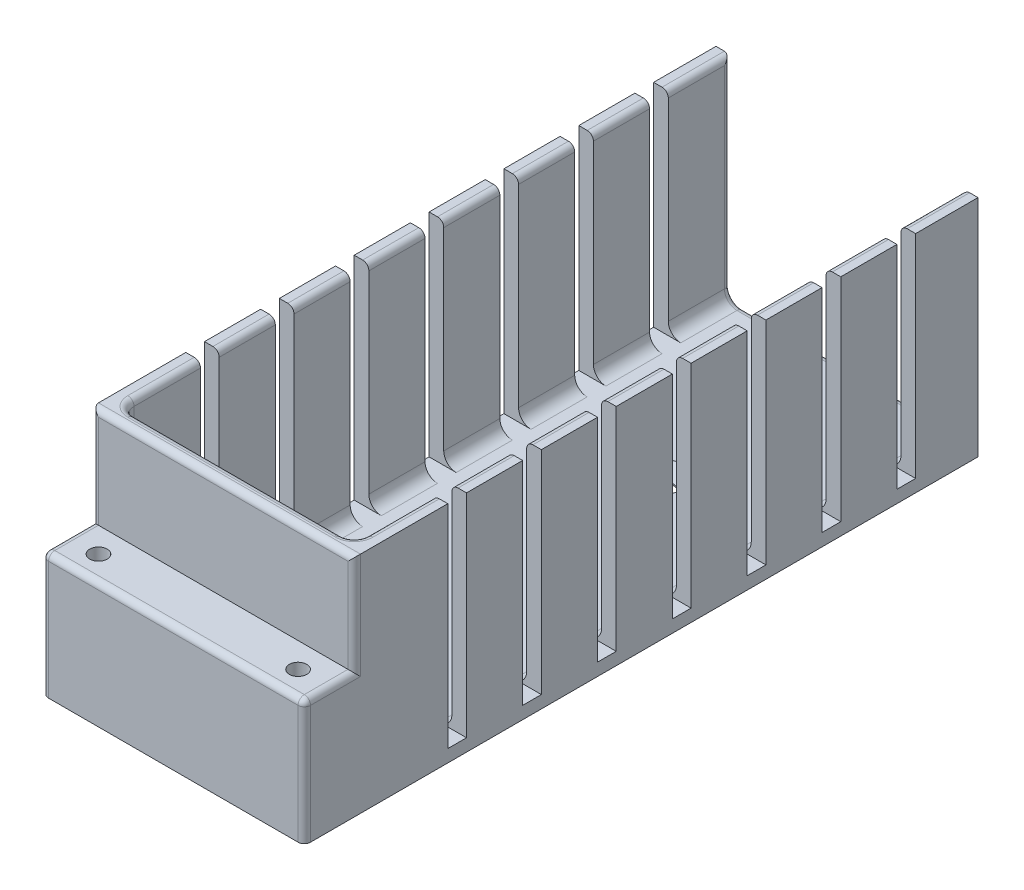
SolidWorks part; units mm, degrees
ref_plane "Front Plane" through (0, 0, 0) normal (0, 0, 1) x (1, 0, 0)
ref_plane "Top Plane" through (0, 0, 0) normal (0, 1, 0) x (1, 0, 0)
ref_plane "Right Plane" through (0, 0, 0) normal (1, 0, 0) x (0, 0, -1)
sketch "Sketch1" plane through (0, 0, 0) normal (0, 1, 0) x (1, 0, 0)
  line L1 (-21, -50) -> (21, -50)
  line L2 (-21, -50) -> (-21, 50)
  line L3 (-21, 50) -> (21, 50)
  line L4 (21, -50) -> (21, 50)
  line L5 (-21, -50) -> (21, 50) construction
  line L6 (-21, 50) -> (21, -50) construction
  point P0 (0, 0)
  dimension "D1" = 42
  dimension "D2" = 100
extrude "Boss-Extrude1" add sketch "Sketch1" along normal blind 2
sketch "Sketch2" plane through (0, 2, 0) normal (0, 1, 0) x (1, 0, 0)
  line L0 (-21, 50) -> (-18.65, 50)
  line L1 (21, 50) -> (-21, 50) construction
  line L2 (-18.65, 50) -> (-18.65, -47.65)
  line L3 (-18.65, -47.65) -> (18.65, -47.65)
  line L4 (21, -50) -> (21, 50)
  line L5 (21, 50) -> (-21, 50)
  line L6 (-21, 50) -> (-21, -50)
  line L7 (-21, -50) -> (21, -50)
  line L8 (21, -50) -> (21, 50)
  line L10 (-21, 50) -> (-21, -50)
  line L11 (-21, -50) -> (21, -50)
  line L12 (18.65, -47.65) -> (18.65, 50)
  line L13 (18.65, 50) -> (21, 50)
  line L14 (0, -47.65) -> (0, 0) construction
  line L15 (0, -47.65) -> (0, -50) construction
  dimension "D2" = 37.3
  dimension "D1" = 0
extrude "Boss-Extrude2" add sketch "Sketch2" along normal blind 34
fillet "Fillet1" radius 2 5 edges at (18.65, 2, -1.175) (0, 2, 47.65) (-18.65, 2, -1.175) (18.65, 19, 47.65) (-18.65, 19, 47.65)
sketch "Sketch3" plane through (0, 36, 0) normal (0, 1, 0) x (1, 0, 0)
  line L0 (-21, 50) -> (-21, -50) construction
  line L1 (-21, 40) -> (21, 40)
  line L2 (-21, 40) -> (-21, 37)
  line L3 (-21, 37) -> (21, 37)
  line L4 (21, 40) -> (21, 37)
  line L5 (21, -50) -> (21, 50) construction
  line L6 (21, 50) -> (18.65, 50) construction
  dimension "D1" = 10
  dimension "D2" = 3
extrude "Cut-Extrude1" cut sketch "Sketch3" against normal up to surface (34 mm away) up to face at (0, 2, -2.175)
pattern_linear "LPattern1" count 7 spacing 12 along (0, 0, 1) of "Cut-Extrude1"
sketch "Sketch4" plane through (0, 2, 0) normal (0, 1, 0) x (1, 0, 0)
  circle A0 centre (0.5607, 20) radius 1.4 construction
  circle A1 centre (0.5607, 20) radius 1.4 construction
  circle A2 centre (0.5607, -20) radius 1.4 construction
  circle A3 centre (0.5607, -20) radius 1.4 construction
hole_wizard "CSK for M3 Flat Head Machine Screw1" positions "3DSketch1" profile "Sketch5" countersink size "M3" standard "ANSI Metric" end condition through all
sketch3d "3DSketch1"
  point P0 (0.5607, 2, -20)
  point P3 (0.5607, 2, 20)
sketch "Sketch5" plane through (0.5607, 2, -20) normal (1, 0, 0) x (0, 0, 1)
  line L0 (0, 0) -> (0, 2)
  line L1 (0, 2) -> (1.6, 2)
  line L2 (1.6, 2) -> (1.6, 1.775)
  line L3 (1.6, 1.775) -> (3.375, 0)
  line L5 (3.375, 0) -> (0, 0)
  line L6 (-1.6, 1.775) -> (-3.375, 0) construction
  line L11 (0, -6.35) -> (0, 107.95) construction
  dimension "Thru Hole Dia." = 3.2
  dimension "Thru Hole Depth" = 2
  dimension "Near C'Sink Dia." = 6.75
  dimension "Near C'Sink Angle" = 90
sketch "Sketch7" plane through (0, 0, 0) normal (0, -1, 0) x (1, 0, 0)
  line L0 (-21, 50) -> (-21, 58)
  line L1 (-21, 58) -> (21, 58)
  line L2 (21, 58) -> (21, 50)
  line L3 (21, 50) -> (-21, 50)
  line L4 (-16, 54) -> (16, 54) construction
  circle A0 centre (-16, 54) radius 1.4
  circle A1 centre (16, 54) radius 1.4
  dimension "D1" = 2.8
  dimension "D2" = 5
  dimension "D3" = 5
  dimension "D4" = 4
  dimension "D5" = 8
extrude "Boss-Extrude3" add sketch "Sketch7" against normal blind 20
fillet "Fillet2" radius 1 32 edges at (18.65, 36, 40.325) (18.0642, 36, 47.0642) (-18.65, 36, 40.325) (-18.0642, 36, 47.0642) (0, 36, 47.65) (18.65, 36, -45) (18.65, 36, -32.5) (18.65, 36, -20.5) (18.65, 36, -8.5) (18.65, 36, 3.5) (-18.65, 36, 3.5) (-18.65, 36, -8.5) (-18.65, 36, -20.5) (-18.65, 36, -32.5) (-18.65, 36, -45) (18.65, 36, 27.5) (18.65, 36, 15.5) (-18.65, 36, 15.5) (-18.65, 36, 27.5) (21, 28, 50) (-21, 28, 50) (18.65, 20, -50) (18.0642, 2.5858, -50) (-18.65, 20, -50) (-18.0642, 2.5858, -50) (0, 2, -50) (0, 36, 50) (-21, 20, 54) (21, 20, 54) (21, 10, 58) (-21, 10, 58) (0, 20, 58)
